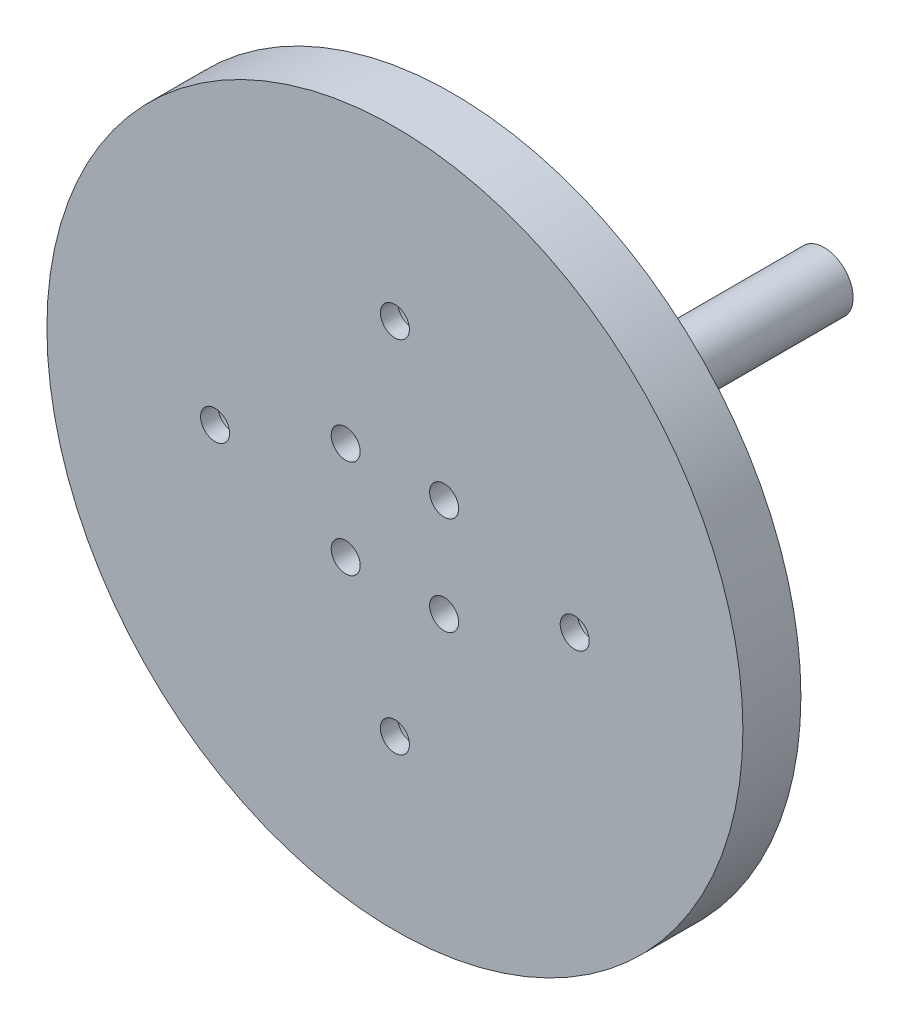
SolidWorks part; units mm, degrees
ref_plane "Front Plane" through (0, 0, 0) normal (0, 0, 1) x (1, 0, 0)
ref_plane "Top Plane" through (0, 0, 0) normal (0, 1, 0) x (1, 0, 0)
ref_plane "Right Plane" through (0, 0, 0) normal (1, 0, 0) x (0, 0, -1)
sketch "Sketch1" plane through (0, 0, 0) normal (0, 0, 1) x (1, 0, 0)
  circle A0 centre (0, 0) radius 30
extrude "Boss-Extrude1" add sketch "Sketch1" along normal blind 5
sketch "Sketch2" plane through (0, 0, 5) normal (0, 0, 1) x (1, 0, 0)
  line L0 (0, 15.5) -> (0, 0) construction
  line L1 (0, 0) -> (4.2426, 4.2426) construction
  circle A0 centre (0, 15.5) radius 1.25
  circle A1 centre (15.5, 0) radius 1.25
  circle A2 centre (0, -15.5) radius 1.25
  circle A3 centre (-15.5, 0) radius 1.25
  circle A4 centre (4.2426, 4.2426) radius 1.25
  circle A5 centre (4.2426, -4.2426) radius 1.25
  circle A6 centre (-4.2426, -4.2426) radius 1.25
  circle A7 centre (-4.2426, 4.2426) radius 1.25
  point P12 (0, 0)
  point P21 (0, 0)
  dimension "D1" = 15.5
  dimension "D3" = 2.5
  dimension "D4" = 2.5
  dimension "D5" = 6
  dimension "D7" = 45
  dimension "D2" = 4
  dimension "D6" = 4
extrude "Cut-Extrude1" cut sketch "Sketch2" against normal blind 5
sketch "Sketch3" plane through (0, 0, 0) normal (0, 0, -1) x (-1, 0, 0)
  circle A0 centre (0, 0) radius 2.5
extrude "Boss-Extrude2" add sketch "Sketch3" along normal blind 32
sketch "Sketch4" [suppressed] plane through (0, 0, 5) normal (0, 0, 1) x (1, 0, 0)
  circle A0 centre (0, 0) radius 2.5
extrude "Boss-Extrude3" [suppressed] add sketch "Sketch4" along normal blind 25
sketch "Sketch5" plane through (0, 0, 0) normal (0, 0, -1) x (-1, 0, 0)
  circle A0 centre (15.5, 0) radius 2.75
  circle A1 centre (0, -15.5) radius 2.75
  circle A2 centre (-15.5, 0) radius 2.75
  circle A3 centre (0, 15.5) radius 2.75
  point P12 (0, 0)
  dimension "D1" = 5.5
  dimension "D2" = 4
extrude "Cut-Extrude2" cut sketch "Sketch5" against normal blind 3.5
